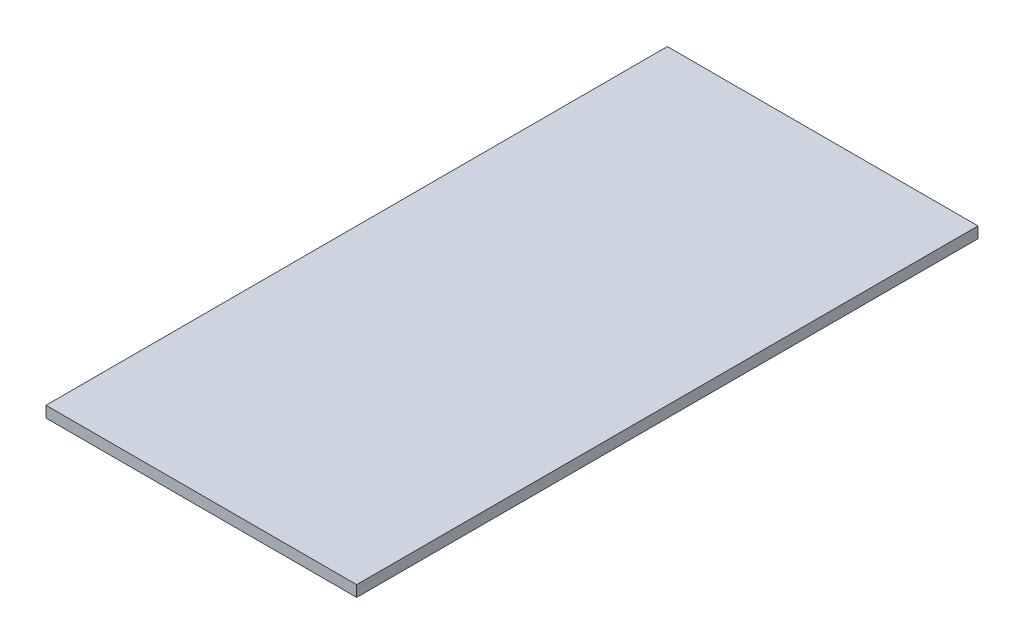
SolidWorks part; units mm, degrees
material "PC High Viscosity"
ref_plane "Front Plane" through (0, 0, 0) normal (0, 0, 1) x (1, 0, 0)
ref_plane "Top Plane" through (0, 0, 0) normal (0, 1, 0) x (1, 0, 0)
ref_plane "Right Plane" through (0, 0, 0) normal (1, 0, 0) x (0, 0, -1)
sketch "Sketch1" plane through (0, 0, 0) normal (0, 1, 0) x (1, 0, 0)
  line L1 (-88.9, -177.8) -> (88.9, -177.8)
  line L2 (-88.9, -177.8) -> (-88.9, 177.8)
  line L3 (-88.9, 177.8) -> (88.9, 177.8)
  line L4 (88.9, -177.8) -> (88.9, 177.8)
  line L5 (-88.9, -177.8) -> (88.9, 177.8) construction
  line L6 (-88.9, 177.8) -> (88.9, -177.8) construction
  point P0 (0, 0)
  dimension "D1" = 177.8
  dimension "D2" = 355.6
extrude "Boss-Extrude1" add sketch "Sketch1" along normal blind 6.35
